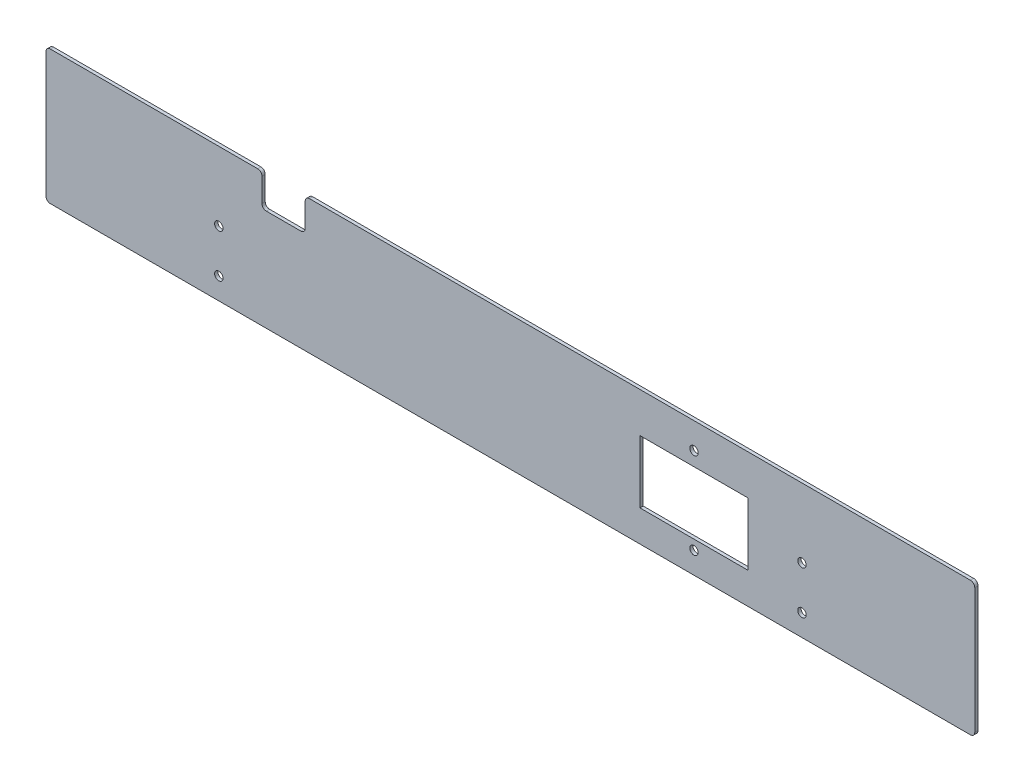
SolidWorks part; units mm, degrees
ref_plane "Front Plane" through (0, 0, 0) normal (0, 0, 1) x (1, 0, 0)
ref_plane "Top Plane" through (0, 0, 0) normal (0, 1, 0) x (1, 0, 0)
ref_plane "Right Plane" through (0, 0, 0) normal (1, 0, 0) x (0, 0, -1)
sketch "Sketch1" plane through (0, 0, 0) normal (0, 0, 1) x (1, 0, 0)
  line L0 (-234.4248, 29.7035) -> (75.5752, 29.7035)
  line L1 (-354.4248, 29.7035) -> (-254.4248, 29.7035)
  line L2 (-354.4248, 29.7035) -> (-354.4248, -32.2965)
  line L3 (-354.4248, -32.2965) -> (75.5752, -32.2965)
  line L4 (75.5752, 29.7035) -> (75.5752, -32.2965)
  line L5 (-79.4248, 11.2035) -> (-29.4248, 11.2035)
  line L6 (-79.4248, 11.2035) -> (-79.4248, -17.7965)
  line L7 (-79.4248, -17.7965) -> (-29.4248, -17.7965)
  line L8 (-29.4248, 11.2035) -> (-29.4248, -17.7965)
  line L10 (-234.4248, 29.7035) -> (-234.4248, 14.7035)
  line L11 (-234.4248, 14.7035) -> (-254.4248, 14.7035)
  line L12 (-254.4248, 29.7035) -> (-254.4248, 14.7035)
  circle A0 centre (-54.4248, 17.7035) radius 1.95
  circle A1 centre (-54.4248, -22.2965) radius 1.95
  point P12 (-54.4248, 11.2035)
  dimension "D3" = 105
  dimension "D4" = 40
  dimension "D1" = 430
  dimension "D2" = 62
  dimension "D5" = 10
  dimension "D6" = 50
  dimension "D7" = 29
  dimension "D8" = 6.5
  dimension "D9" = 20
  dimension "D10" = 100
  dimension "D11" = 15
extrude "Boss-Extrude1" add sketch "Sketch1" along normal blind 1.5
fillet "Fillet1" radius 2 8 edges at (75.5752, -32.2965, 0.75) (-354.4248, -32.2965, 0.75) (-354.4248, 29.7035, 0.75) (-234.4248, 14.7035, 0.75) (-254.4248, 14.7035, 0.75) (-254.4248, 29.7035, 0.75) (-234.4248, 29.7035, 0.75) (75.5752, 29.7035, 0.75)
sketch "Sketch3" plane through (0, 0, 0) normal (0, 0, -1) x (-1, 0, 0)
  line L0 (352.4248, -32.2965) -> (-73.5752, -32.2965) construction
  line L1 (-75.5752, -30.2965) -> (-75.5752, 27.7035) construction
  line L2 (354.4248, 27.7035) -> (354.4248, -30.2965) construction
  circle A0 centre (4.4248, -22.2965) radius 1.95
  circle A1 centre (4.4248, -2.2965) radius 1.95
  circle A2 centre (274.4248, -22.2965) radius 1.95
  circle A3 centre (274.4248, -2.2965) radius 1.95
  dimension "D1" = 10
  dimension "D3" = 20
  dimension "D4" = 80
  dimension "D2" = 80
  dimension "D5" = 20
  dimension "D6" = 10
extrude "Cut-Extrude1" cut sketch "Sketch3" against normal blind 10
